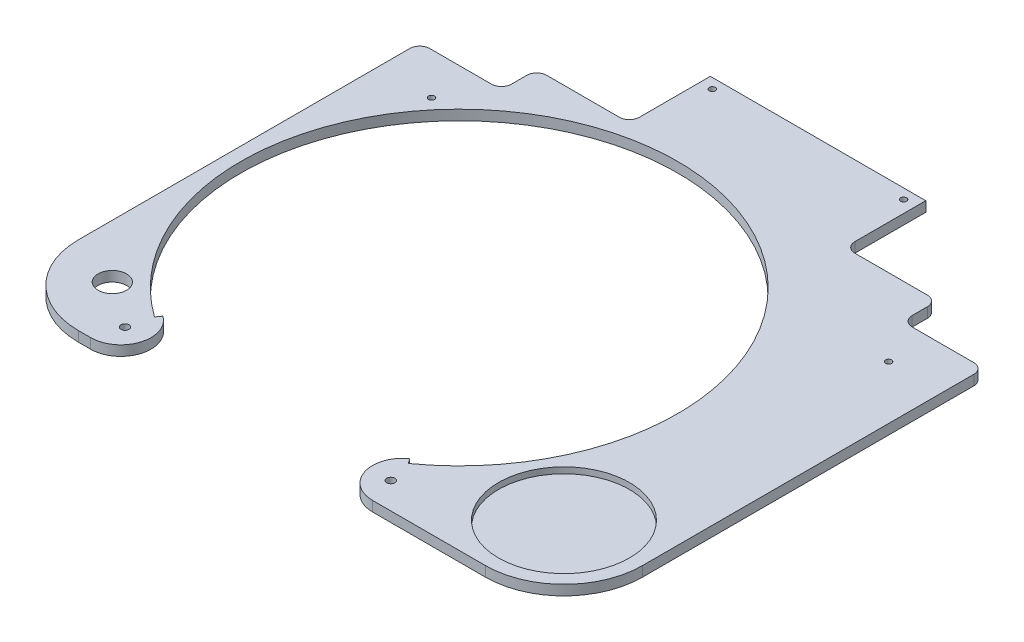
SolidWorks part; units mm, degrees
material "ABS PC"
ref_plane "Plan de face" through (0, 0, 0) normal (0, 0, 1) x (1, 0, 0)
ref_plane "Plan de dessus" through (0, 0, 0) normal (0, 1, 0) x (1, 0, 0)
ref_plane "Plan de droite" through (0, 0, 0) normal (1, 0, 0) x (0, 0, -1)
sketch "Esquisse1" plane through (0, 0, 0) normal (0, 1, 0) x (1, 0, 0)
  line L0 (-101.1, -245.0829) -> (-95, -245.0829) construction
  line L1 (-140.1, 31.2) -> (140.1, 31.2)
  line L2 (-140.1, 31.2) -> (-140.1, -245.0829)
  line L3 (-140.1, -245.0829) -> (140.1, -245.0829)
  line L4 (140.1, 31.2) -> (140.1, -245.0829)
  line L8 (-114.5, 31.2) -> (114.5, 31.2) construction
  line L9 (-140.1, 4) -> (-140.1, -4) construction
  line L10 (140.1, -4) -> (140.1, 4) construction
extrude "Boss.-Extru.1" add sketch "Esquisse1" along normal blind 5
sketch "Esquisse2" plane through (0, 5, 0) normal (0, 1, 0) x (1, 0, 0)
  line L1 (-86.2863, -217.8734) -> (-88.029, -220.3153) construction
  line L2 (-86.2863, -217.8734) -> (-88.029, -220.3153)
  line L3 (45, -245.0829) -> (-95, -245.0829)
  line L5 (36.2863, -217.8734) -> (38.029, -220.3153)
  line L6 (-140.1, -245.0829) -> (140.1, -245.0829) construction
  line L7 (36.2863, -217.8734) -> (38.029, -220.3153) construction
  arc A0 (-95, -245.0829) -> (-86.2863, -217.8734) centre (-95, -230.0829) ccw construction
  arc A2 (-25, -23.5) -> (-88.029, -220.3153) centre (-25, -132) ccw construction
  arc A3 (-25, -23.5) -> (-88.029, -220.3153) centre (-25, -132) ccw
  arc A4 (-95, -245.0829) -> (-86.2863, -217.8734) centre (-95, -230.0829) ccw
  arc A6 (36.2863, -217.8734) -> (45, -245.0829) centre (45, -230.0829) ccw
  arc A7 (38.029, -220.3153) -> (-25, -23.5) centre (-25, -132) ccw
  arc A8 (36.2863, -217.8734) -> (45, -245.0829) centre (45, -230.0829) ccw construction
extrude "Enlèv. mat.-Extru.1" cut sketch "Esquisse2" against normal through all
sketch "Esquisse4" plane through (0, 5, 0) normal (0, 1, 0) x (1, 0, 0)
  line L0 (140.1, -245.0829) -> (101.1, -245.0829)
  line L1 (140.1, -245.0829) -> (140.1, -206.0829)
  line L2 (-101.1, -245.0829) -> (-140.1, -245.0829)
  line L3 (-140.1, -245.0829) -> (-140.1, -206.0829)
  arc A1 (101.1, -245.0829) -> (140.1, -206.0829) centre (101.1, -206.0829) ccw
  arc A3 (-140.1, -206.0829) -> (-101.1, -245.0829) centre (-101.1, -206.0829) ccw
  arc A4 (101.1, -245.0829) -> (140.1, -206.0829) centre (101.1, -206.0829) ccw construction
  arc A5 (-140.1, -206.0829) -> (-101.1, -245.0829) centre (-101.1, -206.0829) ccw construction
extrude "Enlèv. mat.-Extru.3" cut sketch "Esquisse4" against normal through all
sketch "Esquisse5" plane through (0, 5, 0) normal (0, 1, 0) x (1, 0, 0)
  circle A0 centre (-91, -232) radius 2 construction
  circle A1 centre (-91, -232) radius 2
  circle A2 centre (41, -232) radius 2 construction
  circle A3 centre (41, -232) radius 2
extrude "Enlèv. mat.-Extru.4" cut sketch "Esquisse5" against normal through all
sketch "Esquisse6" plane through (0, 5, 0) normal (0, 1, 0) x (1, 0, 0)
  line L0 (99.5, 0) -> (99.5, 26.9) construction
  line L1 (140.1, 31.2) -> (0, 31.2)
  line L2 (140.1, 31.2) -> (140.1, -41.5125)
  line L3 (135.1, -36.5125) -> (104.5, -36.5125)
  line L4 (99.5, -24) -> (99.5, -31.5125)
  line L5 (94.5, -19) -> (58.5, -19)
  line L6 (53.5, -14) -> (53.5, 21.2)
  line L7 (53.5, 21.2) -> (-53.5, 21.2)
  line L8 (-82.5, 21.2) -> (82.5, 21.2) construction
  line L9 (55.5, 15) -> (55.5, -15) construction
  line L10 (88, -16) -> (89, -16) construction
  line L11 (-53.5, -14) -> (-53.5, 21.2)
  line L12 (-94.5, -19) -> (-58.5, -19)
  line L13 (-99.5, -24) -> (-99.5, -31.5125)
  line L14 (120.5, -36.5125) -> (130.66, -36.5125) construction
  line L15 (-135.1, -36.5125) -> (-104.5, -36.5125)
  line L16 (-140.1, 31.2) -> (-140.1, -41.5125)
  line L17 (-140.1, 31.2) -> (0, 31.2)
  line L25 (0, 0) -> (0, 86.4947) construction
  line L27 (140.1, 36.5125) -> (140.1, -245.0829) construction
  line L36 (140.1, 31.2) -> (-140.1, 31.2) construction
  arc A0 (140.1, -41.5125) -> (135.1, -36.5125) centre (135.1, -41.5125) ccw
  arc A1 (-99.5, -24) -> (-94.5, -19) centre (-94.5, -24) cw
  arc A2 (58.5, -19) -> (53.5, -14) centre (58.5, -14) cw
  arc A3 (-104.5, -36.5125) -> (-99.5, -31.5125) centre (-104.5, -31.5125) ccw
  arc A4 (104.5, -36.5125) -> (99.5, -31.5125) centre (104.5, -31.5125) cw
  arc A5 (99.5, -24) -> (94.5, -19) centre (94.5, -24) ccw
  arc A6 (-58.5, -19) -> (-53.5, -14) centre (-58.5, -14) ccw
  arc A7 (-140.1, -41.5125) -> (-135.1, -36.5125) centre (-135.1, -41.5125) cw
  point P41 (99.5, -36.5125)
  point P43 (99.5, -19)
  point P49 (0, 21.2)
  dimension "D1" = 5
  dimension "D2" = 2
  dimension "D3" = 3
extrude "Enlèv. mat.-Extru.5" cut sketch "Esquisse6" against normal through all
sketch "Esquisse7" plane through (0, 5, 0) normal (0, 1, 0) x (1, 0, 0)
  circle A1 centre (-113.5, -215.8) radius 7.0711
extrude "Enlèv. mat.-Extru.6" cut sketch "Esquisse7" against normal through all
sketch "Esquisse8" plane through (0, 0, 0) normal (0, -1, 0) x (1, 0, 0)
  line L1 (-114.5, -21.2) -> (114.5, -21.2) construction
  line L2 (0, 0) -> (0, -63.4963) construction
  circle A1 centre (47.5, -16.2) radius 1.5
  circle A2 centre (-47.5, -16.2) radius 1.5
  dimension "D4" = 3
  dimension "D2" = 5
  dimension "D3" = 95
extrude "Enlèv. mat.-Extru.8" cut sketch "Esquisse8" against normal through all
sketch "Esquisse9" plane through (0, 5, 0) normal (0, 1, 0) x (1, 0, 0)
  circle A0 centre (101.1, -206.0829) radius 32.5
  circle A1 centre (101.1, -206.0829) radius 32 construction
  dimension "D1" = 65
extrude "Enlèv. mat.-Extru.10" cut sketch "Esquisse9" against normal blind 3
sketch "Esquisse10" plane through (0, 5, 0) normal (0, 1, 0) x (1, 0, 0)
  line L0 (113.5, -57.265) -> (118.5, -57.265) construction
  line L1 (118.5, -55.765) -> (118.5, -58.765) construction
  line L2 (-118.5, -57.265) -> (-113.5, -57.265) construction
  line L3 (-118.5, -58.765) -> (-118.5, -55.765) construction
  circle A0 centre (113.5, -57.265) radius 1.5
  circle A1 centre (-113.5, -57.265) radius 1.5
  dimension "D2" = 3
  dimension "D1" = 5
extrude "Enlèv. mat.-Extru.11" cut sketch "Esquisse10" against normal through all
